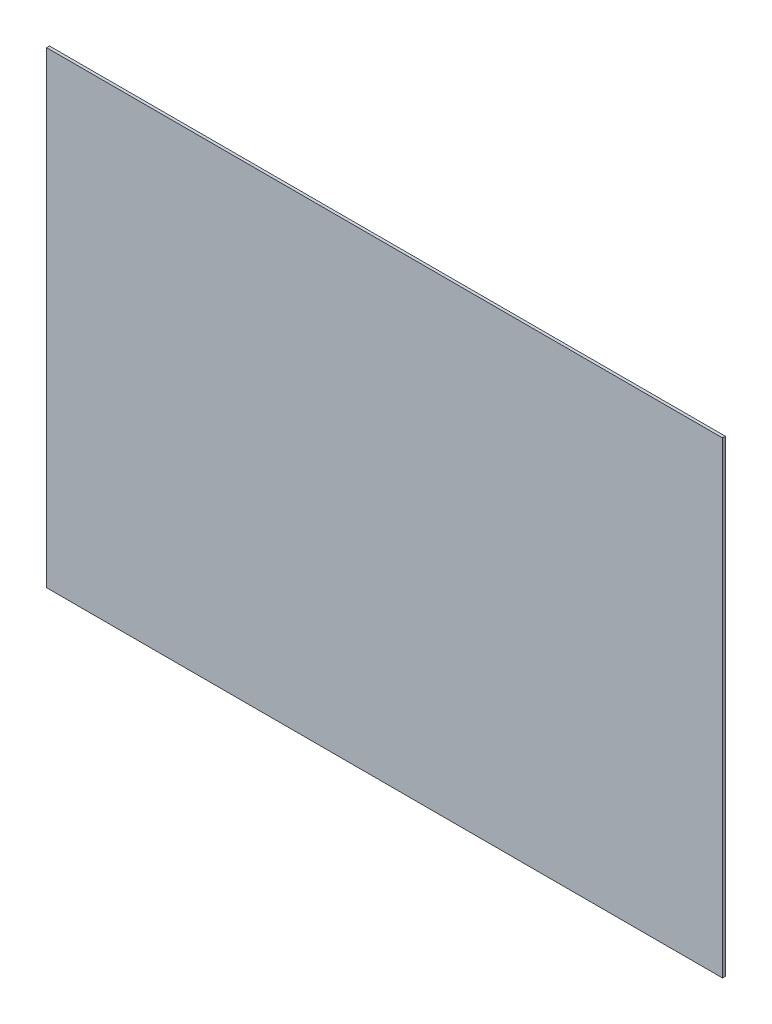
SolidWorks part; units mm, degrees
material "Mahogany"
ref_plane "Front Plane" through (0, 0, 0) normal (0, 0, 1) x (1, 0, 0)
ref_plane "Top Plane" through (0, 0, 0) normal (0, 1, 0) x (1, 0, 0)
ref_plane "Right Plane" through (0, 0, 0) normal (1, 0, 0) x (0, 0, -1)
sketch "Sketch1" plane through (0, 0, 0) normal (0, 0, 1) x (1, 0, 0)
  line L1 (-372.5, 257.8) -> (372.5, 257.8)
  line L2 (-372.5, 257.8) -> (-372.5, -257.8)
  line L3 (-372.5, -257.8) -> (372.5, -257.8)
  line L4 (372.5, 257.8) -> (372.5, -257.8)
  line L5 (-372.5, 257.8) -> (372.5, -257.8) construction
  line L6 (-372.5, -257.8) -> (372.5, 257.8) construction
  point P0 (0, 0)
  dimension "D1" = 745
  dimension "D2" = 515.6
extrude "Boss-Extrude1" add sketch "Sketch1" along normal blind 3.175
equation "\"W\"= 1700"
equation "\"L\"= 760"
equation "\"H\"= 810"
equation "\"ARM_BOLT_SPACING\"= 140"
equation "\"ARM_TO_WALL\"= 300"
equation "\"D1@Sketch1\"=\"L\"-15"
equation "\"D2@Sketch1\"=\"H\"-(15+279.4)"
